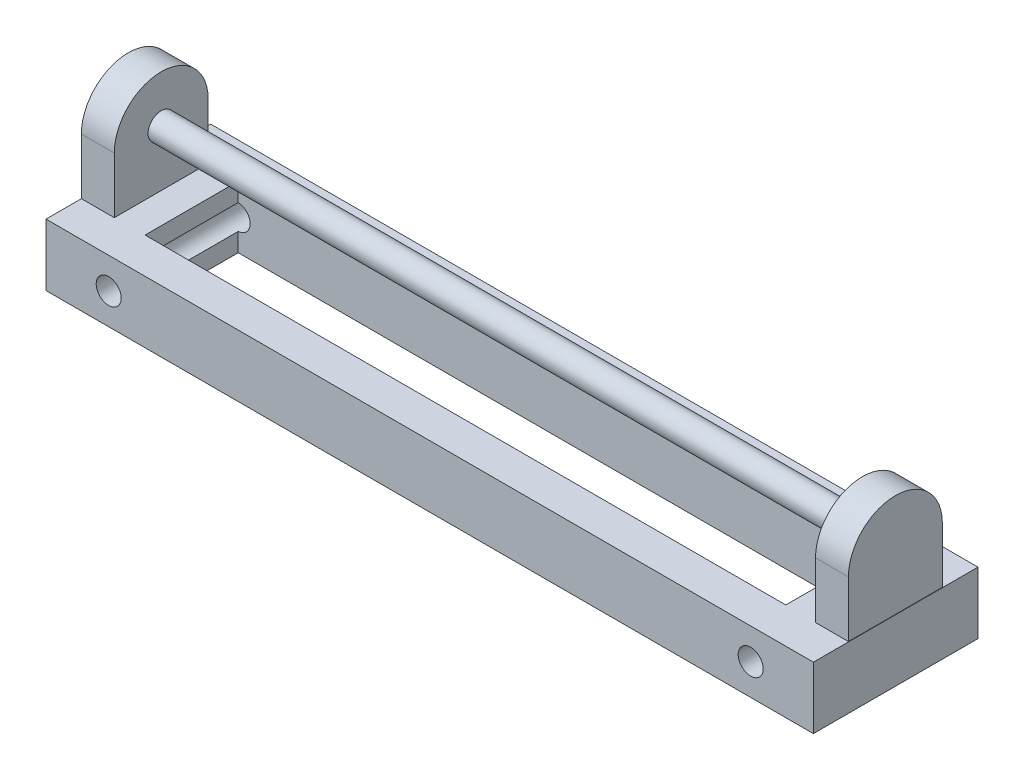
SolidWorks part; units mm, degrees
ref_plane "Front Plane" through (0, 0, 0) normal (0, 0, 1) x (1, 0, 0)
ref_plane "Top Plane" through (0, 0, 0) normal (0, 1, 0) x (1, 0, 0)
ref_plane "Right Plane" through (0, 0, 0) normal (1, 0, 0) x (0, 0, -1)
sketch "Sketch1" plane through (0, 0, 0) normal (0, 0, 1) x (1, 0, 0)
  line L0 (-29.0663, -19.4201) -> (-29.0663, -0.613)
  line L1 (-29.0663, -0.613) -> (204.0331, -0.613)
  line L2 (204.0331, -0.613) -> (204.0331, -19.4201)
  line L3 (204.0331, -19.4201) -> (-29.0663, -19.4201)
  line L4 (-29.0663, -10.0166) -> (204.0331, -10.0166) construction
  circle A0 centre (-10.0166, -10.0166) radius 3.7971
  circle A1 centre (184.9834, -10.0166) radius 3.7971
  dimension "D1" = 233.0994
extrude "Boss-Extrude1" add sketch "Sketch1" along normal blind 50 contours L4 L0 L3 L2 A1 A0 | L0 L4 A0 A1 L2 L1 region at (87.4834, -14.7835, 0) region at (87.4834, -5.2496, 0)
sketch "Sketch2" plane through (0, -0.613, 0) normal (0, 1, 0) x (1, 0, 0)
  line L0 (-29.0663, -25) -> (204.0331, -25) construction
  line L1 (-29.0663, -50) -> (-29.0663, 0) construction
  line L2 (204.0331, -50) -> (204.0331, 0) construction
sketch "Sketch3" plane through (-29.0663, 0, 0) normal (-1, 0, 0) x (0, 0, 1)
  line L0 (10.7435, -0.613) -> (10.7435, 16.3932)
  line L1 (50, -0.613) -> (0, -0.613) construction
  line L2 (39.2565, 16.3932) -> (39.2565, -0.613)
  line L3 (39.2565, -0.613) -> (10.7435, -0.613)
  line L4 (25, 16.3932) -> (25, -0.613) construction
  arc A0 (10.7435, 16.3932) -> (39.2565, 16.3932) centre (25, 16.3932) cw
  circle A1 centre (25, 16.3932) radius 4.0011
extrude "Boss-Extrude2" add sketch "Sketch3" against normal blind 10
extrude "Boss-Extrude5" add sketch "Sketch3<2>" along normal blind 10 from offset 233 offset against normal yes
sketch "Sketch3<2>" plane through (-29.0663, 0, 0) normal (-1, 0, 0) x (0, 0, 1) same geometry as "Sketch3"
sketch "Sketch4" plane through (203.9337, 0, 0) normal (1, 0, 0) x (0, 0, -1)
  circle A0 centre (-25, 16.3932) radius 4.0011
  dimension "D1" = 8.0022
extrude "Boss-Extrude6" add sketch "Sketch4" against normal blind 233
sketch "Sketch5" plane through (0, -19.4201, 0) normal (0, -1, 0) x (1, 0, 0)
  line L0 (87.4834, 39.1524) -> (87.4834, 10.8476) construction
  line L1 (-9.8273, 39.1524) -> (184.7942, 39.1524)
  line L2 (-9.8273, 39.1524) -> (-9.8273, 10.8476)
  line L3 (-9.8273, 10.8476) -> (184.7942, 10.8476)
  line L4 (184.7942, 39.1524) -> (184.7942, 10.8476)
  line L5 (184.7942, 25) -> (-9.8273, 25) construction
  line L6 (-29.0663, 25) -> (204.0331, 25) construction
  line L7 (184.7942, 25) -> (204.0331, 25) construction
  line L8 (204.0331, 50) -> (204.0331, 0) construction
  line L9 (-9.8273, 25) -> (-29.0663, 25) construction
  line L10 (-29.0663, 50) -> (-29.0663, 0) construction
extrude "Cut-Extrude1" cut sketch "Sketch5" against normal up to next
